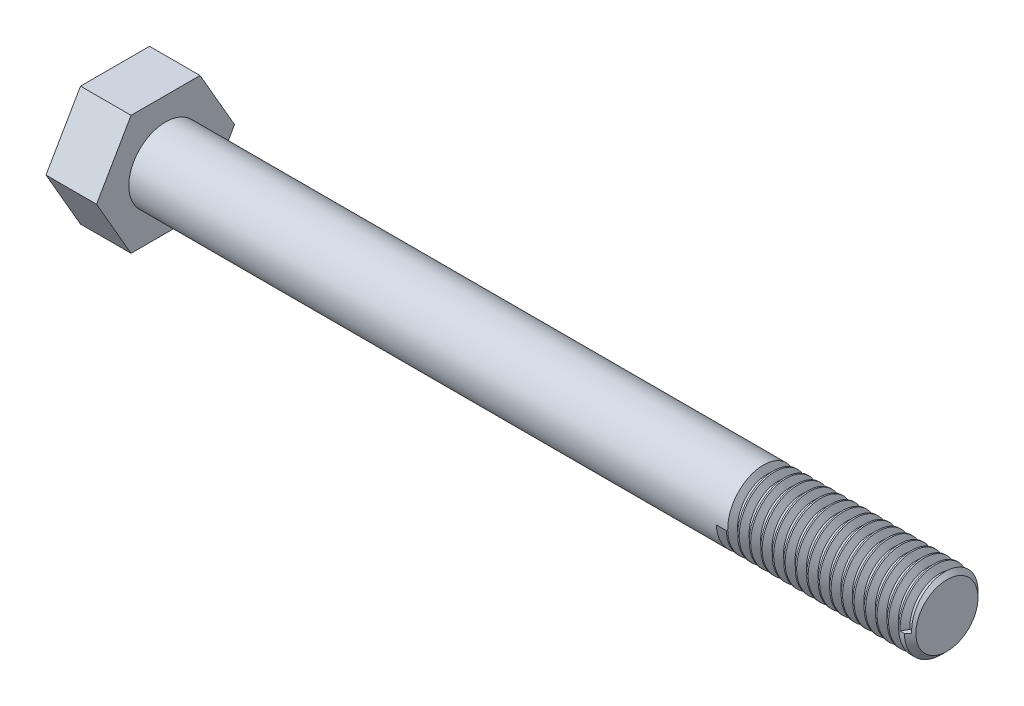
SolidWorks part; units mm, degrees
ref_plane "Front Plane" through (0, 0, 0) normal (0, 0, 1) x (1, 0, 0)
ref_plane "Top Plane" through (0, 0, 0) normal (0, 1, 0) x (1, 0, 0)
ref_plane "Right Plane" through (0, 0, 0) normal (1, 0, 0) x (0, 0, -1)
sketch "Sketch1" plane through (0, 0, 0) normal (0, 0, 1) x (1, 0, 0)
  line L0 (0, 0) -> (85, 0) construction
  line L1 (85, 0) -> (85, 4)
  line L2 (85, 4) -> (0, 4)
  line L6 (0, 0) -> (85, 0)
  line L7 (0, 4) -> (0, 0)
  dimension "D1" = 4
  dimension "D2" = 85
revolve "Revolve1" add sketch "Sketch1" angle 360 about L0
sketch "Sketch2" plane through (0, 0, 0) normal (-1, 0, 0) x (0, 0, 1)
  line L1 (7.5056, 0) -> (3.7528, 6.5)
  line L2 (3.7528, 6.5) -> (-3.7528, 6.5)
  line L3 (-3.7528, 6.5) -> (-7.5056, 0)
  line L4 (-7.5056, 0) -> (-3.7528, -6.5)
  line L5 (-3.7528, -6.5) -> (3.7528, -6.5)
  line L6 (3.7528, -6.5) -> (7.5056, 0)
  circle A0 centre (0, 0) radius 6.5 construction
  dimension "D1" = 13
extrude "Boss-Extrude1" add sketch "Sketch2" along normal blind 5.5
thread "Thread1" pitch 1.25 method cut profile "Thread Profile1" start angle 0, offset 0, length 20, pitch 1.25, diameter 8
ref_plane "Plane1" through (85, 0, 4) normal (0, -1, 0) x (0, 0, 1)
sketch "Thread Profile1" plane through (85, 0, 4) normal (0, -1, 0) x (0, 0, 1)
  line L0 (0, 0) -> (0, 1.25) construction
  line L11 (0, 0) -> (0, 1.0937)
  line L12 (0, 1.0937) -> (-0.6766, 0.7031)
  line L13 (-0.6766, 0.7031) -> (-0.6766, 0.3906)
  line L15 (-0.6766, 0.3906) -> (0, 0)
  line L17 (-0.6766, 0.5469) -> (0, 0.5469) construction
  point P2 (0, 0)
  dimension "Pitch" = 1.25
  dimension "Profile_Angle" = 60
  dimension "Profile_Land" = 0.3125
  dimension "Profile_Height" = 0.6766
chamfer "Chamfer1" distance 0.62 angle 45 1 edges at (85, -4, 0)
